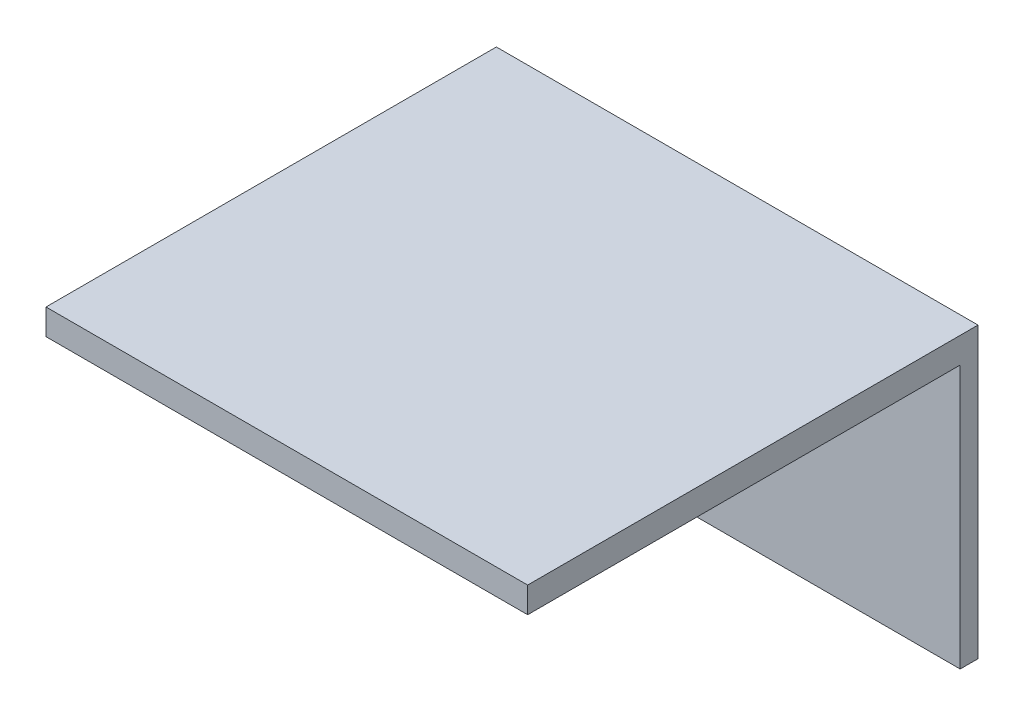
SolidWorks part; units mm, degrees
ref_plane "Ebene vorne" through (0, 0, 0) normal (0, 0, 1) x (1, 0, 0)
ref_plane "Ebene oben" through (0, 0, 0) normal (0, 1, 0) x (1, 0, 0)
ref_plane "Ebene rechts" through (0, 0, 0) normal (1, 0, 0) x (0, 0, -1)
sketch "Skizze1" plane through (0, 0, 0) normal (0, 0, 1) x (1, 0, 0)
  line L1 (-500, 300) -> (500, 300)
  line L2 (-500, 300) -> (-500, -300)
  line L3 (-500, -300) -> (500, -300)
  line L4 (500, 300) -> (500, -300)
  line L5 (-500, 300) -> (500, -300) construction
  line L6 (-500, -300) -> (500, 300) construction
  point P0 (0, 0)
  dimension "D1" = 600
  dimension "D2" = 1000
extrude "Aufsatz-Linear austragen1" add sketch "Skizze1" along normal blind 37
sketch "Skizze2" plane through (0, 0, 37) normal (0, 0, 1) x (1, 0, 0)
  line L0 (500, -300) -> (500, 300) construction
  line L1 (-500, 300) -> (500, 300)
  line L2 (-500, 300) -> (-500, 246.5988)
  line L3 (-500, 246.5988) -> (500, 246.5988)
  line L4 (500, 300) -> (500, 246.5988)
extrude "Aufsatz-Linear austragen2" add sketch "Skizze2" along normal blind 898
